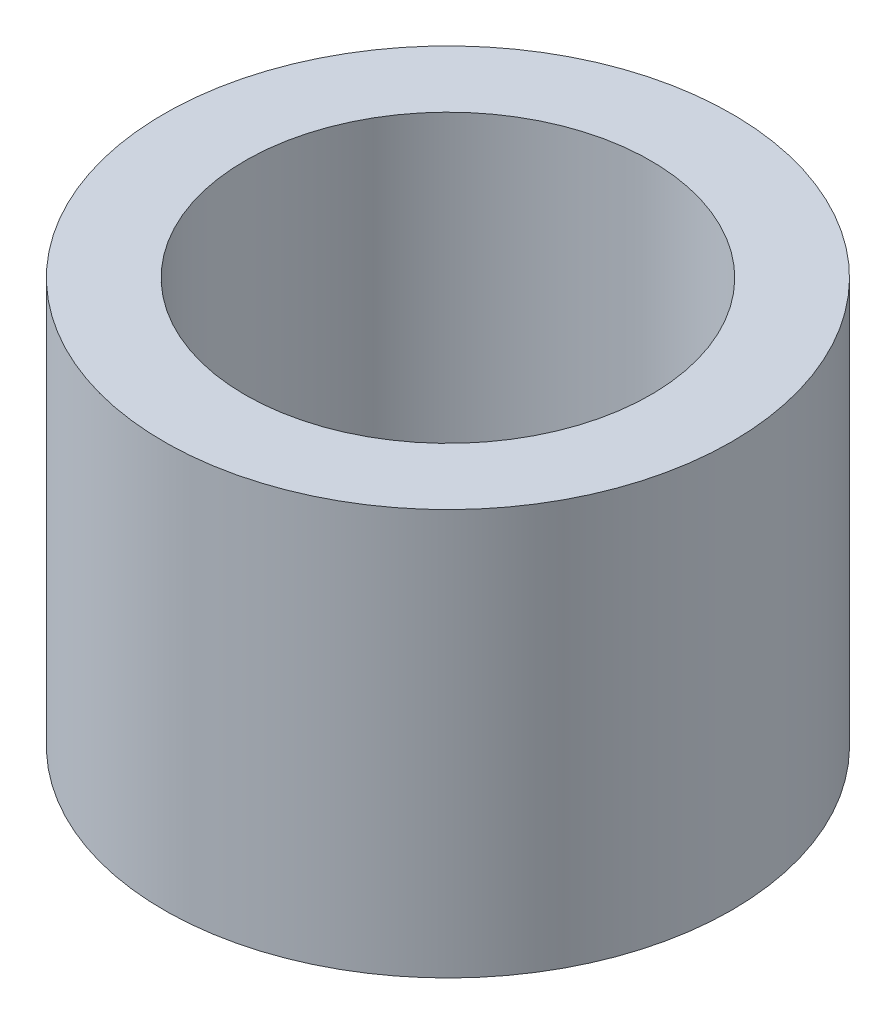
SolidWorks part; units mm, degrees
material "Простая углеродистая сталь"
ref_plane "Спереди" through (0, 0, 0) normal (0, 0, 1) x (1, 0, 0)
ref_plane "Сверху" through (0, 0, 0) normal (0, 1, 0) x (1, 0, 0)
ref_plane "Справа" through (0, 0, 0) normal (1, 0, 0) x (0, 0, -1)
sketch "Эскиз1" plane through (0, 0, 0) normal (0, 1, 0) x (1, 0, 0)
  circle A0 centre (0, 0) radius 25
extrude "Вытянуть-Тонкостенный1" add sketch "Эскиз1" along normal blind 50 thin thin type one direction wall 10
